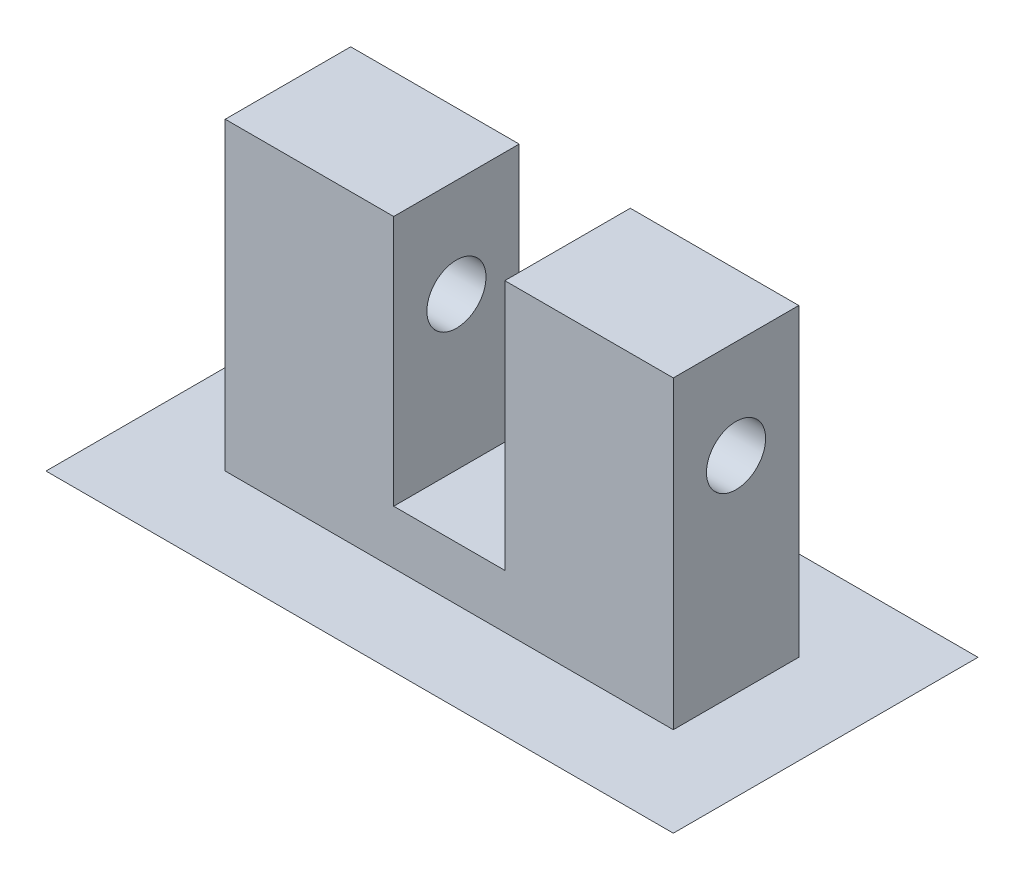
SolidWorks part; units mm, degrees
ref_plane "Front Plane" through (0, 0, 0) normal (0, 0, 1) x (1, 0, 0)
ref_plane "Top Plane" through (0, 0, 0) normal (0, 1, 0) x (1, 0, 0)
ref_plane "Right Plane" through (0, 0, 0) normal (1, 0, 0) x (0, 0, -1)
sketch "Sketch1" plane through (0, 0, 0) normal (0, 1, 0) x (1, 0, 0)
  line L1 (0, 0) -> (25, 0)
  line L2 (0, 0) -> (0, 7)
  line L3 (0, 7) -> (25, 7)
  line L4 (25, 0) -> (25, 7)
  dimension "D1" = 7
  dimension "D2" = 25
extrude "Boss-Extrude1" add sketch "Sketch1" along normal blind 20
sketch "Sketch2" plane through (0, 0, 0) normal (0, -1, 0) x (1, 0, 0)
  line L0 (-5, -12) -> (-5, 5)
  line L1 (-5, -12) -> (30, -12)
  line L2 (-5, 5) -> (30, 5)
  line L3 (30, -12) -> (30, 5)
  line L4 (-5, -12) -> (30, 5) construction
  line L5 (-5, 5) -> (30, -12) construction
  line L6 (0, 0) -> (25, 0) construction
  line L7 (25, -7) -> (0, -7) construction
  line L8 (0, -7) -> (0, 0) construction
  line L9 (25, 0) -> (25, -7) construction
  point P1 (12.5, -3.5)
  dimension "D1" = 5
  dimension "D2" = 5
  dimension "D3" = 5
  dimension "D4" = 5
extrude "Boss-Extrude2" add sketch "Sketch2" against normal blind 3
chamfer "Chamfer1" distance 3 angle 60 4 edges at (30, 0, -3.5) (12.5, 0, 5) (-5, 0, -3.5) (12.5, 0, -12) first distance on face at (30, 1.5, -3.5) first distance on face at (12.5, 1.5, 5) first distance on face at (-5, 1.5, -3.5) first distance on face at (12.5, 1.5, -12)
sketch "Sketch3" plane through (0, 0, -7) normal (0, 0, -1) x (-1, 0, 0)
  line L0 (-25, 20) -> (0, 20) construction
  line L1 (-15.6, 20) -> (-9.4, 20)
  line L2 (-15.6, 20) -> (-15.6, 6)
  line L3 (-15.6, 6) -> (-9.4, 6)
  line L4 (-9.4, 20) -> (-9.4, 6)
  line L5 (0, 3) -> (-25, 3) construction
  line L6 (0, 20) -> (0, 3) construction
  dimension "D1" = 3
  dimension "D2" = 6.2
  dimension "D3" = 9.4
extrude "Cut-Extrude1" cut sketch "Sketch3" against normal up to surface (7 mm away) up to face at (12.5, 11.5, 0)
sketch "Sketch4" plane through (0, 0, 0) normal (-1, 0, 0) x (0, 0, 1)
  line L0 (-7, 20) -> (0, 20) construction
  circle A0 centre (-3.5, 14.5) radius 1.65
  point P4 (-3.5, 20)
  dimension "D1" = 3.3
  dimension "D2" = 5.5
extrude "Cut-Extrude2" cut sketch "Sketch4" against normal up to surface (25 mm away) up to face at (25, 11.5, -3.5)
sketch "Sketch5" [suppressed] plane through (0, 15, 0) normal (0, 1, 0) x (1, 0, 0)
  line L0 (25, 0) -> (0, 0) construction
  line L1 (0, 7) -> (9.4, 7)
  line L2 (0, 7) -> (0, 0)
  line L3 (0, 0) -> (9.4, 0)
  line L4 (9.4, 7) -> (9.4, 0)
  line L5 (0, 0) -> (9.4, 0) construction
  line L7 (15.6, 7) -> (25, 7)
  line L8 (15.6, 7) -> (15.6, 0)
  line L9 (15.6, 0) -> (25, 0)
  line L10 (25, 7) -> (25, 0)
